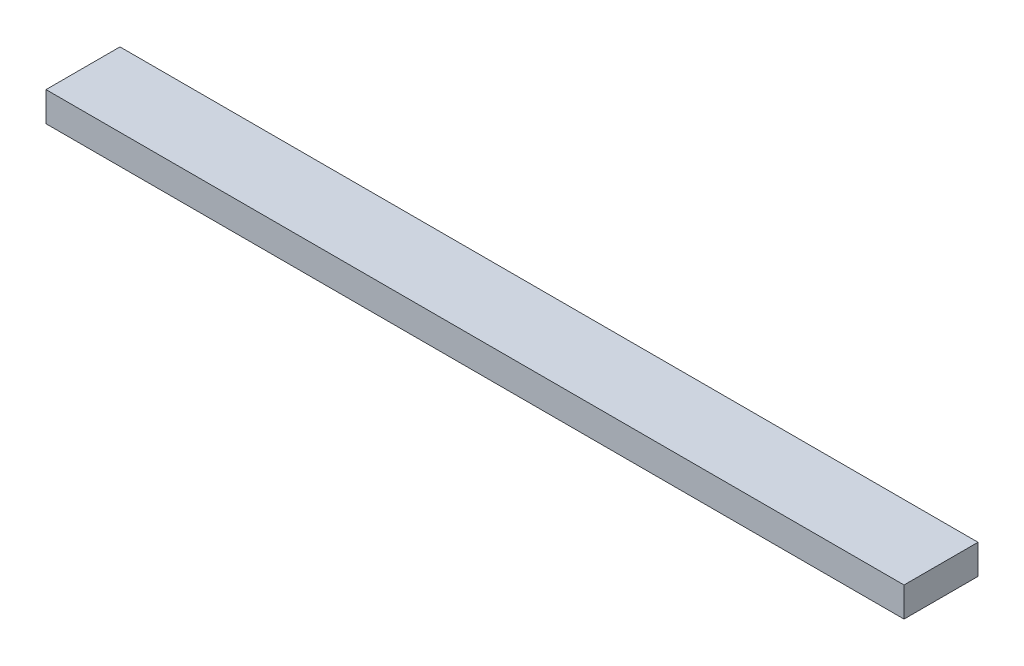
SolidWorks part; units mm, degrees
material "Сосна"
ref_plane "Спереди" through (0, 0, 0) normal (0, 0, 1) x (1, 0, 0)
ref_plane "Сверху" through (0, 0, 0) normal (0, 1, 0) x (1, 0, 0)
ref_plane "Справа" through (0, 0, 0) normal (1, 0, 0) x (0, 0, -1)
sketch "Эскиз1" plane through (0, 0, 0) normal (0, 1, 0) x (1, 0, 0)
  line L1 (0, 0) -> (290, 0)
  line L2 (0, 0) -> (0, 25)
  line L3 (0, 25) -> (290, 25)
  line L4 (290, 0) -> (290, 25)
  dimension "D1" = 25
  dimension "D2" = 290
extrude "Бобышка-Вытянуть1" add sketch "Эскиз1" along normal blind 10
